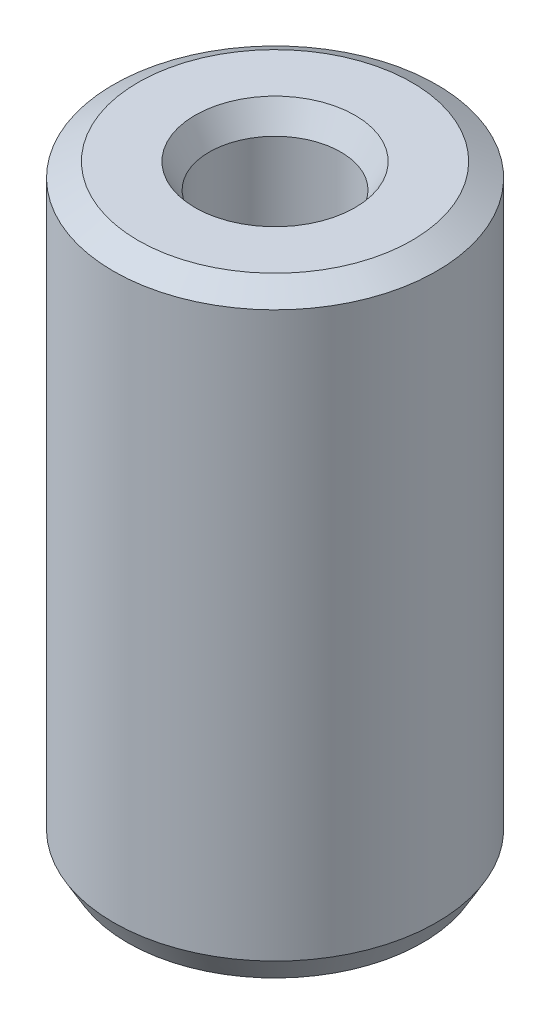
SolidWorks part; units mm, degrees
ref_plane "Front Plane" through (0, 0, 0) normal (0, 0, 1) x (1, 0, 0)
ref_plane "Top Plane" through (0, 0, 0) normal (0, 1, 0) x (1, 0, 0)
ref_plane "Right Plane" through (0, 0, 0) normal (1, 0, 0) x (0, 0, -1)
sketch "Sketch1" plane through (0, 0, 0) normal (0, 1, 0) x (1, 0, 0)
  circle A0 centre (0, 0) radius 5
  dimension "SLEEVE_OD" = 10
extrude "Boss-Extrude1" add sketch "Sketch1" along normal blind 18.6533
sketch "Sketch2" plane through (0, 0, 0) normal (0, 1, 0) x (1, 0, 0)
  circle A0 centre (0, 0) radius 2.0343
  dimension "BORE_D" = 4.0687
extrude "Cut-Extrude1" cut sketch "Sketch2" along normal through all
chamfer "Chamfer1" distance 0.4411 angle 60 4 edges at (0, 18.6533, 2.0343) (0, 0, 2.0343) (0, 0, 5) (0, 18.6533, 5) first distance on face at (0, 18.6533, 2.0343) first distance on face at (0, 0, 2.0343) first distance on face at (0, 18.6533, 5)
